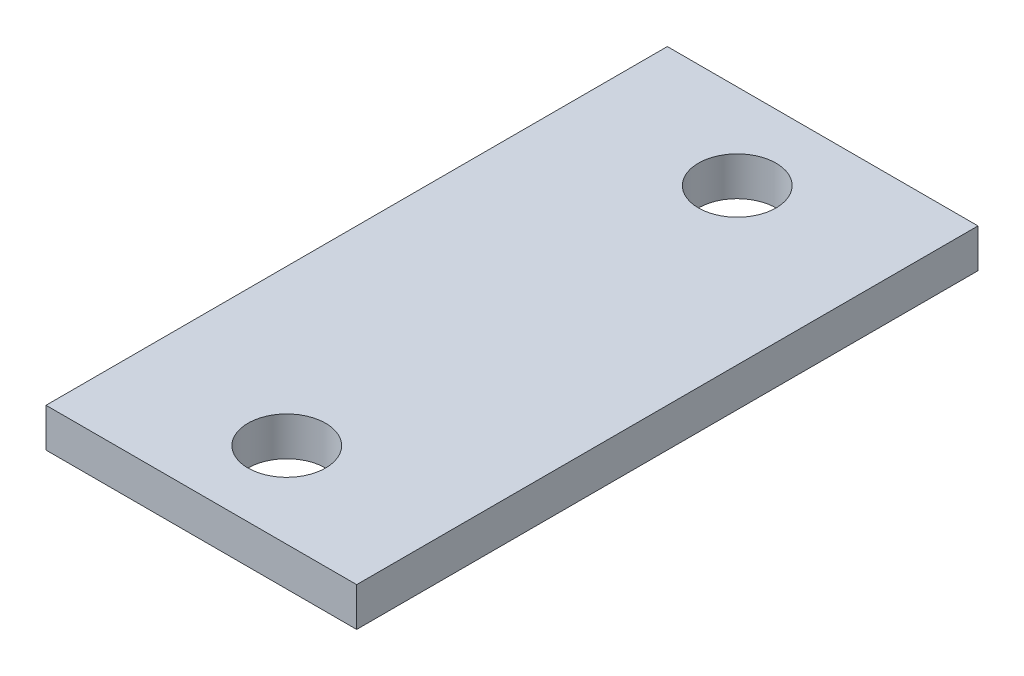
SolidWorks part; units mm, degrees
material "Plain Carbon Steel"
ref_plane "Front Plane" through (0, 0, 0) normal (0, 0, 1) x (1, 0, 0)
ref_plane "Top Plane" through (0, 0, 0) normal (0, 1, 0) x (1, 0, 0)
ref_plane "Right Plane" through (0, 0, 0) normal (1, 0, 0) x (0, 0, -1)
sketch "Sketch1" plane through (0, 0, 0) normal (0, 1, 0) x (1, 0, 0)
  line L1 (0, 0) -> (50.8, 0)
  line L2 (0, 0) -> (0, 101.6)
  line L3 (0, 101.6) -> (50.8, 101.6)
  line L4 (50.8, 0) -> (50.8, 101.6)
  line L8 (0, 13.97) -> (50.8, 13.97) construction
  circle A0 centre (25.4, 13.97) radius 6.35
  circle A1 centre (25.4, 87.63) radius 6.35
  dimension "D6" = 12.7
  dimension "D1" = 101.6
  dimension "D2" = 87.63
  dimension "D3" = 25.4
  dimension "D5" = 50.8
  dimension "D7" = 87.63
extrude "Hammer" add sketch "Sketch1" along normal blind 6.35
